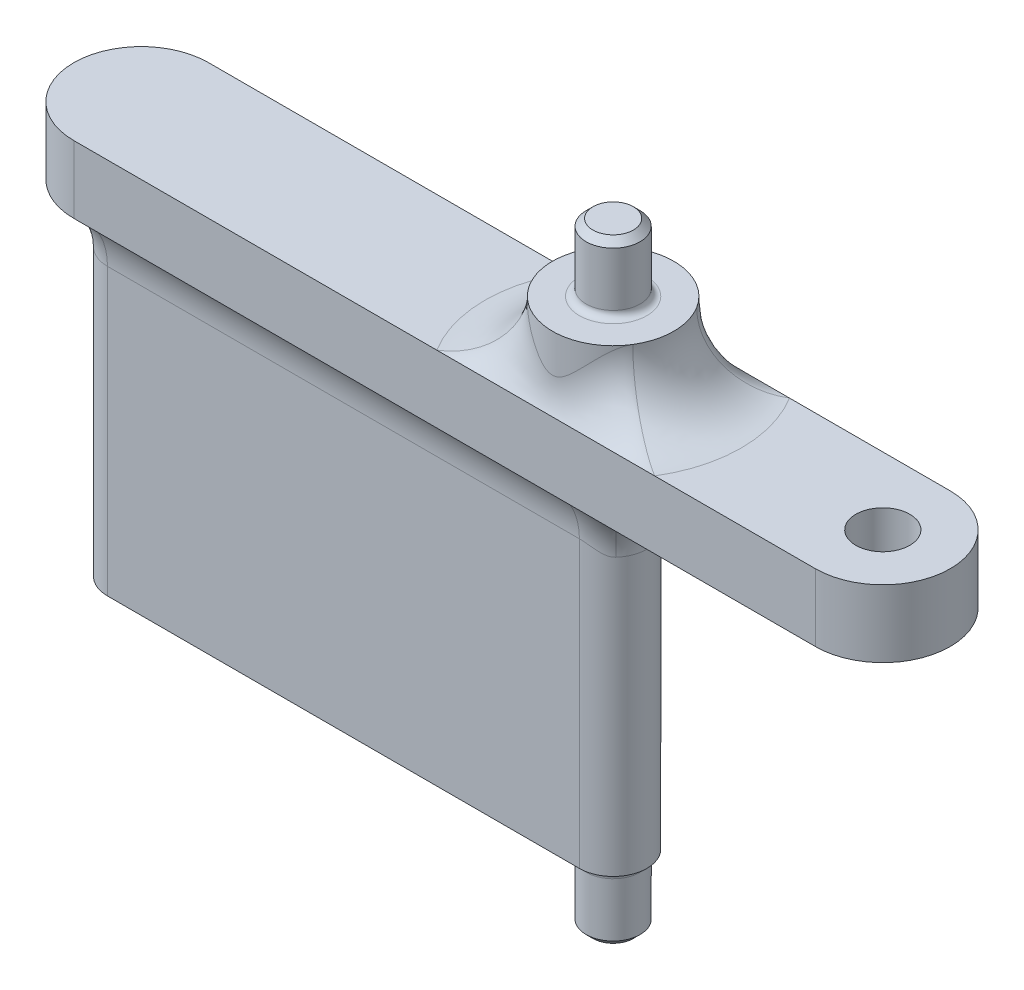
SolidWorks part; units mm, degrees
ref_plane "Front Plane" through (0, 0, 0) normal (0, 0, 1) x (1, 0, 0)
ref_plane "Top Plane" through (0, 0, 0) normal (0, 1, 0) x (1, 0, 0)
ref_plane "Right Plane" through (0, 0, 0) normal (1, 0, 0) x (0, 0, -1)
sketch "Sketch1" plane through (0, 0, 0) normal (0, 1, 0) x (1, 0, 0)
  line L0 (0, 0) -> (-70, 0) construction
  line L1 (0, -5) -> (-70, -5)
  line L2 (0, 5) -> (-70, 5)
  arc A0 (0, -5) -> (0, 5) centre (0, 0) ccw
  arc A1 (-70, 5) -> (-70, -5) centre (-70, 0) ccw
  point P3 (-35, 0)
  dimension "D1" = 70
  dimension "D2" = 10
extrude "Boss-Extrude1" add sketch "Sketch1" against normal blind 51
sketch "Sketch2" plane through (0, 0, 0) normal (0, 1, 0) x (1, 0, 0)
  line L0 (0, 0) -> (-70, 0) construction
  line L5 (0, -10) -> (-70, -10)
  line L6 (0, 10) -> (-70, 10)
  line L7 (0, 0) -> (40, 0) construction
  line L8 (0, 10) -> (40, 10)
  line L9 (0, -10) -> (40, -10)
  arc A5 (-70, 10) -> (-70, -10) centre (-70, 0) ccw
  arc A7 (40, -10) -> (40, 10) centre (40, 0) ccw
  circle A8 centre (40, 0) radius 4
  dimension "D5" = 8
  dimension "D7" = 10
  dimension "D1" = 70
  dimension "D2" = 20
  dimension "D3" = 20
  dimension "D4" = 40
  dimension "D6" = 70
extrude "Boss-Extrude2" add sketch "Sketch2" along normal blind 10
fillet "Fillet1" radius 10 1 edges at (5, 0, 0)
sketch "Sketch3" plane through (0, 10, 0) normal (0, 1, 0) x (1, 0, 0)
  circle A0 centre (0, 0) radius 9
  dimension "D1" = 18
extrude "Boss-Extrude3" add sketch "Sketch3" along normal blind 10
fillet "Fillet2" radius 10 1 edges at (0, 10, 9)
sketch "Sketch7" plane through (0, -51, 0) normal (0, -1, 0) x (1, 0, 0)
  circle A0 centre (0, 0) radius 4
  dimension "D1" = 8
extrude "Boss-Extrude4" add sketch "Sketch7" along normal blind 10
chamfer "Chamfer1" distance 1 angle 45 1 edges at (0, -61, -4)
sketch "Sketch8" plane through (0, 20, 0) normal (0, 1, 0) x (1, 0, 0)
  circle A1 centre (0, 0) radius 4
  dimension "D1" = 8
extrude "Boss-Extrude5" add sketch "Sketch8" along normal blind 10
chamfer "Chamfer2" distance 1 angle 45 1 edges at (0, 30, 4)
fillet "Fillet3" radius 1 1 edges at (0, 20, 4)
fillet "Fillet4" radius 1 1 edges at (0, -51, 4)
